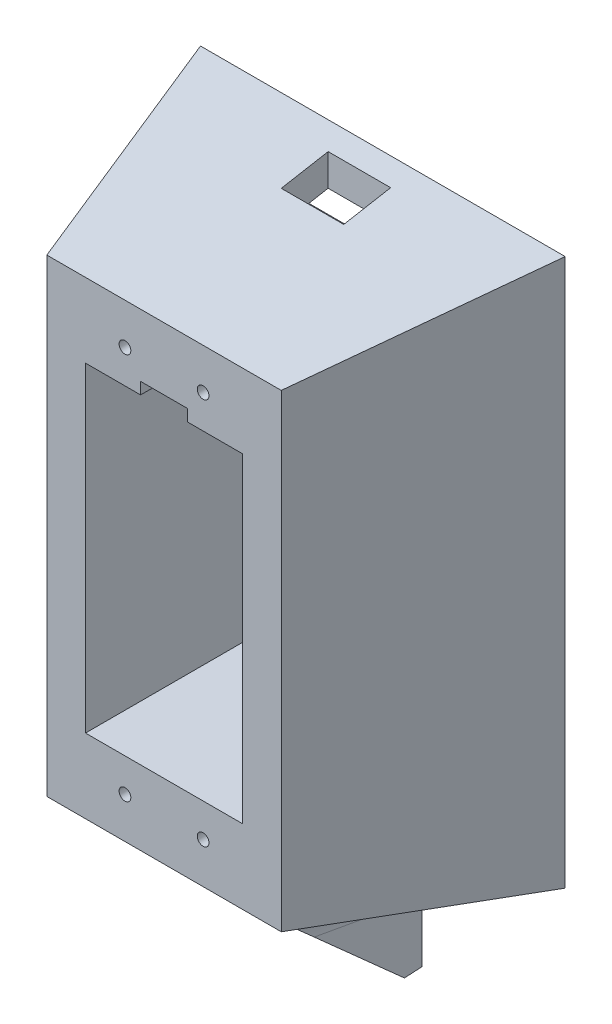
SolidWorks part; units mm, degrees
ref_plane "Plano frontal" through (0, 0, 0) normal (0, 0, 1) x (1, 0, 0)
ref_plane "Plano superior" through (0, 0, 0) normal (0, 1, 0) x (1, 0, 0)
ref_plane "Plano direito" through (0, 0, 0) normal (1, 0, 0) x (0, 0, -1)
sketch "Esboço1" plane through (0, 0, 0) normal (0, 0, 1) x (1, 0, 0)
  line L1 (-15, -30) -> (15, -30)
  line L2 (-15, -30) -> (-15, 30)
  line L3 (-15, 30) -> (15, 30)
  line L4 (15, -30) -> (15, 30)
  line L5 (-15, -30) -> (15, 30) construction
  line L6 (-15, 30) -> (15, -30) construction
  point P0 (0, 0)
  dimension "D1" = 60
ref_plane "Plano1" through (0, 0, -28) normal (0, 0, 1) x (1, 0, 0)
sketch "Esboço2" plane through (0, 0, -28) normal (0, 0, 1) x (1, 0, 0)
  line L1 (-23.3333, -35) -> (23.3333, -35)
  line L2 (-23.3333, -35) -> (-23.3333, 35)
  line L3 (-23.3333, 35) -> (23.3333, 35)
  line L4 (23.3333, -35) -> (23.3333, 35)
  line L5 (-23.3333, -35) -> (23.3333, 35) construction
  line L6 (-23.3333, 35) -> (23.3333, -35) construction
  dimension "D1" = 70
loft "Loft1" add profiles "Esboço1", "Esboço2" connector at (-15, -30, 0) connector at (-23.3333, -35, -28)
sketch "Esboço3" plane through (0, 0, 0) normal (0, 0, 1) x (1, 0, 0)
  line L1 (-10.05, -20.5) -> (10.05, -20.5)
  line L2 (-10.05, -20.5) -> (-10.05, 20.5)
  line L3 (-10.05, 20.5) -> (10.05, 20.5)
  line L4 (10.05, -20.5) -> (10.05, 20.5)
  line L5 (-10.05, -20.5) -> (10.05, 20.5) construction
  line L6 (-10.05, 20.5) -> (10.05, -20.5) construction
  point P0 (0, 0)
  dimension "D1" = 41
extrude "Corte-extrusão1" cut sketch "Esboço3" against normal through all
shell "Casca1" thickness 4 removed face at (0, 0, -28)
sketch "Esboço5" plane through (0, 0, -28) normal (0, 0, 1) x (1, 0, 0)
  line L0 (0, 0) -> (0, 6.0662) construction
  line L1 (0, 0) -> (5.9294, 0) construction
  line L31 (10.05, 20.5) -> (10.05, 30.9367)
  line L32 (19.1599, 30.9367) -> (-19.1599, 30.9367) construction
  line L33 (10.05, 30.9367) -> (19.1599, 30.9367)
  line L34 (19.1599, 30.9367) -> (19.1599, 20.5)
  line L35 (19.1599, -30.9367) -> (19.1599, 30.9367) construction
  line L36 (19.1599, 20.5) -> (10.05, 20.5)
  line L37 (19.1599, -20.5) -> (10.05, -20.5)
  line L38 (19.1599, -30.9367) -> (19.1599, -20.5)
  line L39 (10.05, -30.9367) -> (19.1599, -30.9367)
  line L40 (10.05, -20.5) -> (10.05, -30.9367)
  line L41 (-10.05, -20.5) -> (-10.05, -30.9367)
  line L42 (-10.05, -30.9367) -> (-19.1599, -30.9367)
  line L43 (-19.1599, -30.9367) -> (-19.1599, -20.5)
  line L44 (-19.1599, -20.5) -> (-10.05, -20.5)
  line L45 (-19.1599, 20.5) -> (-10.05, 20.5)
  line L46 (-19.1599, 30.9367) -> (-19.1599, 20.5)
  line L47 (-10.05, 30.9367) -> (-19.1599, 30.9367)
  line L48 (-10.05, 20.5) -> (-10.05, 30.9367)
extrude "Ressalto-extrusão3" add sketch "Esboço5" along normal up to next
sketch "Esboço6" plane through (0, 0, -28) normal (0, 0, -1) x (-1, 0, 0)
  line L2 (0, 0) -> (0, 4.4519) construction
  line L3 (0, 0) -> (-5.2651, 0) construction
  circle A0 centre (-15, 25) radius 0.5
  circle A1 centre (15, 25) radius 0.5
  circle A2 centre (15, -25) radius 0.5
  circle A3 centre (-15, -25) radius 0.5
  dimension "D1" = 1
  dimension "D2" = 30
  dimension "D3" = 50
extrude "Corte-extrusão2" cut sketch "Esboço6" against normal blind 5
sketch "Esboço7" plane through (0, 0, 0) normal (0, 0, 1) x (1, 0, 0)
  line L0 (10.05, 20.5) -> (-10.05, 20.5) construction
  line L1 (-5, 24.77) -> (5, 24.77) construction
  line L2 (0, 0) -> (-2.5167, 0) construction
  circle A0 centre (-5, 24.77) radius 0.75
  circle A1 centre (5, 24.77) radius 0.75
  circle A2 centre (-5, -24.77) radius 0.75
  circle A3 centre (5, -24.77) radius 0.75
  point P6 (0, 24.77)
  point P7 (0, 20.5)
  dimension "D1" = 10
  dimension "D3" = 1.5
  dimension "D4" = 1.5
  dimension "D2" = 4.27
extrude "Corte-extrusão3" cut sketch "Esboço7" against normal blind 3
sketch "Esboço8" plane through (0, 0, 0) normal (1, 0, 0) x (0, 0, -1)
  line L0 (28, -35) -> (28, -55)
  line L2 (0, -30) -> (28, -35)
  line L7 (0, -30) -> (28, -55)
  dimension "D1" = 20
extrude "Ressalto-extrusão4" add sketch "Esboço8" along normal mid plane 10
fillet "Filete2" radius 10 2 edges
chamfer "Chanfro3" distance 3 angle 45 1 edges at (0, -55, -28) first distance on face at (-0.625, -37.8867, -8.833)
sketch "Esboço9" plane through (0, 0, -28) normal (0, 0, -1) x (-1, 0, 0)
  line L0 (5, -53.002) -> (-5, -53.002) construction
  circle A0 centre (0, -45.002) radius 0.5
  dimension "D1" = 8
  dimension "D3" = 1
  dimension "D2" = 5
extrude "Corte-extrusão4" cut sketch "Esboço9" against normal blind 3
sketch "Esboço11" plane through (0, -20.5, 0.8002) normal (0, 1, 0) x (1, 0, 0)
  line L6 (-4, 25.8002) -> (4, 25.8002)
  line L8 (-4, 25.8002) -> (-4, 19.8002)
  line L9 (-4, 19.8002) -> (4, 19.8002)
  line L10 (4, 25.8002) -> (4, 19.8002)
  line L11 (-4, 25.8002) -> (4, 19.8002) construction
  line L12 (-4, 19.8002) -> (4, 25.8002) construction
  point P0 (0, 22.8002)
  point P8 (0, 0)
  dimension "D1" = 8
  dimension "D2" = 3
  dimension "D4" = 6
extrude "Corte-extrusão7" cut sketch "Esboço11" along normal through all
sketch "Esboço12" plane through (0, 0, 0) normal (0, 0, 1) x (1, 0, 0)
  line L0 (10.05, 20.5) -> (-10.05, 20.5) construction
  line L1 (-3, 19) -> (3, 19)
  line L2 (-3, 19) -> (-3, 22)
  line L3 (-3, 22) -> (3, 22)
  line L4 (3, 19) -> (3, 22)
  line L5 (-3, 19) -> (3, 22) construction
  line L6 (-3, 22) -> (3, 19) construction
  point P0 (0, 20.5)
  dimension "D1" = 6
  dimension "D2" = 3
extrude "Corte-extrusão6" cut sketch "Esboço12" against normal blind 22
